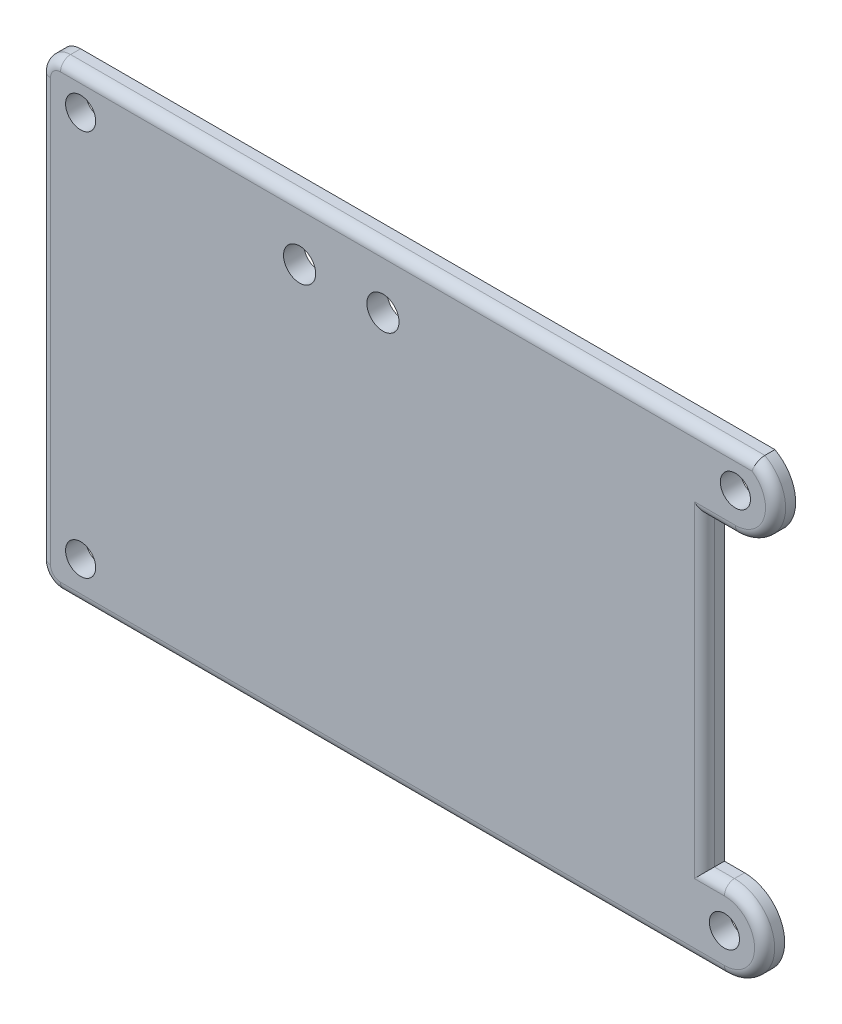
SolidWorks part; units mm, degrees
note: The reader was unsure of these and kept them because the rebuilt part matched: shared geometry of "草图2<6>".
ref_plane "前视基准面" through (0, 0, 0) normal (0, 0, 1) x (1, 0, 0)
ref_plane "上视基准面" through (0, 0, 0) normal (0, 1, 0) x (1, 0, 0)
ref_plane "右视基准面" through (0, 0, 0) normal (1, 0, 0) x (0, 0, -1)
sketch "Model" plane through (0, 0, 0) normal (0, 0, 1) x (1, 0, 0)
  line L0 (0, 2.26) -> (0, 39.4058)
  line L1 (2.4326, 41.5) -> (50.1564, 41.5)
  line L2 (52.5, 39.422) -> (52.5, 2.28)
  line L3 (50.22, 0) -> (2.26, 0)
  line L4 (0.57, 8.85) -> (-6.93, 8.85)
  line L5 (-6.93, 8.85) -> (-6.93, 24.85)
  line L6 (-6.93, 24.85) -> (0.57, 24.85)
  line L7 (16.57, 8.85) -> (17.57, 8.85)
  line L8 (17.57, 8.85) -> (17.57, 10.85)
  line L9 (17.57, 22.85) -> (17.57, 24.85)
  line L10 (17.57, 24.85) -> (16.57, 24.85)
  line L11 (24.196, 8.775) -> (23.307, 8.775)
  line L12 (22.926, 9.156) -> (22.926, 9.664)
  line L13 (23.307, 10.045) -> (24.196, 10.045)
  line L14 (24.704, 10.045) -> (25.593, 10.045)
  line L15 (25.974, 9.664) -> (25.974, 9.156)
  line L16 (25.593, 8.775) -> (24.704, 8.775)
  line L17 (34.756, 17.315) -> (33.867, 17.315)
  line L18 (33.486, 17.696) -> (33.486, 18.204)
  line L19 (33.867, 18.585) -> (34.756, 18.585)
  line L20 (35.264, 18.585) -> (36.153, 18.585)
  line L21 (36.534, 18.204) -> (36.534, 17.696)
  line L22 (36.153, 17.315) -> (35.264, 17.315)
  line L23 (16.835, 4.806) -> (16.835, 3.917)
  line L24 (16.454, 3.536) -> (15.946, 3.536)
  line L25 (15.565, 3.917) -> (15.565, 4.806)
  line L26 (15.565, 5.314) -> (15.565, 6.203)
  line L27 (15.946, 6.584) -> (16.454, 6.584)
  line L28 (16.835, 6.203) -> (16.835, 5.314)
  line L29 (26.454, 3.425) -> (27.343, 3.425)
  line L30 (27.724, 3.044) -> (27.724, 2.536)
  line L31 (27.343, 2.155) -> (26.454, 2.155)
  line L32 (25.946, 2.155) -> (25.057, 2.155)
  line L33 (24.676, 2.536) -> (24.676, 3.044)
  line L34 (25.057, 3.425) -> (25.946, 3.425)
  line L35 (18.255, 4.756) -> (18.255, 3.867)
  line L36 (17.874, 3.486) -> (17.366, 3.486)
  line L37 (16.985, 3.867) -> (16.985, 4.756)
  line L38 (16.985, 5.264) -> (16.985, 6.153)
  line L39 (17.366, 6.534) -> (17.874, 6.534)
  line L40 (18.255, 6.153) -> (18.255, 5.264)
  line L41 (12.8, 35.75) -> (12.8, 38.8)
  line L42 (12.8, 38.8) -> (14.05, 39.95)
  line L43 (14.05, 39.95) -> (16.45, 39.95)
  line L44 (16.45, 39.95) -> (17.6, 38.9)
  line L45 (17.6, 38.9) -> (17.6, 35.7)
  line L46 (17.6, 35.7) -> (16.45, 34.65)
  line L47 (16.45, 34.65) -> (14, 34.65)
  line L48 (14, 34.65) -> (12.8, 35.75)
  line L49 (3.87, 5.53) -> (6.67, 5.53)
  line L50 (6.67, 5.53) -> (6.67, 4.13)
  line L51 (6.67, 4.13) -> (3.87, 4.13)
  line L52 (3.87, 4.13) -> (3.87, 5.53)
  line L53 (20.8, 6.56) -> (20.8, 9.36)
  line L54 (20.8, 9.36) -> (22.2, 9.36)
  line L55 (22.2, 9.36) -> (22.2, 6.56)
  line L56 (22.2, 6.56) -> (20.8, 6.56)
  line L57 (8.21, 6.97) -> (8.21, 4.17)
  line L58 (8.21, 4.17) -> (6.81, 4.17)
  line L59 (6.81, 4.17) -> (6.81, 6.97)
  line L60 (6.81, 6.97) -> (8.21, 6.97)
  line L61 (10.82, 29.94) -> (10.82, 27.14)
  line L62 (10.82, 27.14) -> (9.42, 27.14)
  line L63 (9.42, 27.14) -> (9.42, 29.94)
  line L64 (9.42, 29.94) -> (10.82, 29.94)
  line L65 (33.69, 12.87) -> (30.89, 12.87)
  line L66 (30.89, 12.87) -> (30.89, 14.27)
  line L67 (30.89, 14.27) -> (33.69, 14.27)
  line L68 (33.69, 14.27) -> (33.69, 12.87)
  line L69 (14.93, 29.94) -> (14.93, 27.14)
  line L70 (14.93, 27.14) -> (13.53, 27.14)
  line L71 (13.53, 27.14) -> (13.53, 29.94)
  line L72 (13.53, 29.94) -> (14.93, 29.94)
  line L73 (26.13, 4.53) -> (26.37, 4.53)
  line L74 (26.37, 4.53) -> (26.37, 7.36)
  line L75 (26.37, 7.36) -> (26.13, 7.36)
  line L76 (22.89, 4.53) -> (22.6, 4.53)
  line L77 (22.6, 4.53) -> (22.6, 7.37)
  line L78 (22.6, 7.37) -> (22.87, 7.37)
  line L79 (1.79, 29.79) -> (6.87, 29.79)
  line L80 (6.87, 29.79) -> (6.87, 27.25)
  line L81 (6.87, 27.25) -> (1.79, 27.25)
  line L82 (1.79, 27.25) -> (1.79, 29.79)
  line L83 (29.996, 38.955) -> (29.107, 38.955)
  line L84 (28.726, 39.336) -> (28.726, 39.844)
  line L85 (29.107, 40.225) -> (29.996, 40.225)
  line L86 (30.504, 40.225) -> (31.393, 40.225)
  line L87 (31.774, 39.844) -> (31.774, 39.336)
  line L88 (31.393, 38.955) -> (30.504, 38.955)
  line L89 (35.825, 11.706) -> (35.825, 10.817)
  line L90 (35.444, 10.436) -> (34.936, 10.436)
  line L91 (34.555, 10.817) -> (34.555, 11.706)
  line L92 (34.555, 12.214) -> (34.555, 13.103)
  line L93 (34.936, 13.484) -> (35.444, 13.484)
  line L94 (35.825, 13.103) -> (35.825, 12.214)
  line L95 (31.416, 6.905) -> (30.527, 6.905)
  line L96 (30.146, 7.286) -> (30.146, 7.794)
  line L97 (30.527, 8.175) -> (31.416, 8.175)
  line L98 (31.924, 8.175) -> (32.813, 8.175)
  line L99 (33.194, 7.794) -> (33.194, 7.286)
  line L100 (32.813, 6.905) -> (31.924, 6.905)
  line L101 (27.125, 13.384) -> (27.125, 14.273)
  line L102 (27.506, 14.654) -> (28.014, 14.654)
  line L103 (28.395, 14.273) -> (28.395, 13.384)
  line L104 (28.395, 12.876) -> (28.395, 11.987)
  line L105 (28.014, 11.606) -> (27.506, 11.606)
  line L106 (27.125, 11.987) -> (27.125, 12.876)
  line L107 (2.726, 5.765) -> (1.837, 5.765)
  line L108 (1.456, 6.146) -> (1.456, 6.654)
  line L109 (1.837, 7.035) -> (2.726, 7.035)
  line L110 (3.234, 7.035) -> (4.123, 7.035)
  line L111 (4.504, 6.654) -> (4.504, 6.146)
  line L112 (4.123, 5.765) -> (3.234, 5.765)
  line L113 (38.274, 36.345) -> (39.163, 36.345)
  line L114 (39.544, 35.964) -> (39.544, 35.456)
  line L115 (39.163, 35.075) -> (38.274, 35.075)
  line L116 (37.766, 35.075) -> (36.877, 35.075)
  line L117 (36.496, 35.456) -> (36.496, 35.964)
  line L118 (36.877, 36.345) -> (37.766, 36.345)
  line L119 (35.295, 38.504) -> (35.295, 39.393)
  line L120 (35.676, 39.774) -> (36.184, 39.774)
  line L121 (36.565, 39.393) -> (36.565, 38.504)
  line L122 (36.565, 37.996) -> (36.565, 37.107)
  line L123 (36.184, 36.726) -> (35.676, 36.726)
  line L124 (35.295, 37.107) -> (35.295, 37.996)
  line L125 (31.265, 4.376) -> (31.265, 3.487)
  line L126 (30.884, 3.106) -> (30.376, 3.106)
  line L127 (29.995, 3.487) -> (29.995, 4.376)
  line L128 (29.995, 4.884) -> (29.995, 5.773)
  line L129 (30.376, 6.154) -> (30.884, 6.154)
  line L130 (31.265, 5.773) -> (31.265, 4.884)
  line L131 (33.42, 4.7325) -> (33.42, 6.15)
  line L132 (33.42, 6.15) -> (31.5, 6.15)
  line L133 (31.5, 6.15) -> (31.5, 4.7325)
  line L134 (33.42, 2.8275) -> (33.42, 1.43)
  line L135 (33.42, 1.43) -> (31.5, 1.43)
  line L136 (31.5, 1.43) -> (31.5, 2.8275)
  line L137 (37.99, 12.2925) -> (37.99, 13.71)
  line L138 (37.99, 13.71) -> (36.07, 13.71)
  line L139 (36.07, 13.71) -> (36.07, 12.2925)
  line L140 (37.99, 10.3875) -> (37.99, 8.99)
  line L141 (37.99, 8.99) -> (36.07, 8.99)
  line L142 (36.07, 8.99) -> (36.07, 10.3875)
  line L143 (37.074, 38.3336) -> (37.074, 37.343)
  line L144 (37.582, 36.835) -> (38.6488, 36.835)
  line L145 (39.106, 37.3176) -> (39.106, 38.3336)
  line L146 (37.074, 39.1464) -> (37.074, 40.137)
  line L147 (37.582, 40.645) -> (38.6488, 40.645)
  line L148 (39.106, 40.1624) -> (39.106, 39.1464)
  line L149 (33.975, 16.983) -> (31.689, 16.983)
  line L150 (31.689, 16.983) -> (31.689, 14.697)
  line L151 (31.689, 14.697) -> (33.975, 14.697)
  line L152 (35.245, 16.983) -> (37.15, 16.983)
  line L153 (37.15, 16.983) -> (37.531, 16.602)
  line L154 (37.531, 16.602) -> (37.531, 15.078)
  line L155 (37.531, 15.078) -> (37.15, 14.697)
  line L156 (37.15, 14.697) -> (35.245, 14.697)
  line L157 (21.1, 35.75) -> (21.1, 38.8)
  line L158 (21.1, 38.8) -> (22.35, 39.95)
  line L159 (22.35, 39.95) -> (24.75, 39.95)
  line L160 (24.75, 39.95) -> (25.9, 38.9)
  line L161 (25.9, 38.9) -> (25.9, 35.7)
  line L162 (25.9, 35.7) -> (24.75, 34.65)
  line L163 (24.75, 34.65) -> (22.3, 34.65)
  line L164 (22.3, 34.65) -> (21.1, 35.75)
  line L165 (5.44, 35.75) -> (5.44, 38.8)
  line L166 (5.44, 38.8) -> (6.69, 39.95)
  line L167 (6.69, 39.95) -> (9.09, 39.95)
  line L168 (9.09, 39.95) -> (10.24, 38.9)
  line L169 (10.24, 38.9) -> (10.24, 35.7)
  line L170 (10.24, 35.7) -> (9.09, 34.65)
  line L171 (9.09, 34.65) -> (6.64, 34.65)
  line L172 (6.64, 34.65) -> (5.44, 35.75)
  line L173 (34.57, 3.22) -> (38.57, 3.22)
  line L174 (38.57, 3.22) -> (38.57, 8.72)
  line L175 (38.57, 8.72) -> (34.57, 8.72)
  line L176 (34.57, 8.72) -> (34.57, 3.22)
  line L177 (39.81, 30.07) -> (37.01, 30.07)
  line L178 (37.01, 30.07) -> (37.01, 31.47)
  line L179 (37.01, 31.47) -> (39.81, 31.47)
  line L180 (39.81, 31.47) -> (39.81, 30.07)
  line L181 (28.51, 40.17) -> (28.51, 37.37)
  line L182 (28.51, 37.37) -> (27.11, 37.37)
  line L183 (27.11, 37.37) -> (27.11, 40.17)
  line L184 (27.11, 40.17) -> (28.51, 40.17)
  line L185 (32.06, 40.25) -> (34.86, 40.25)
  line L186 (34.86, 40.25) -> (34.86, 38.85)
  line L187 (34.86, 38.85) -> (32.06, 38.85)
  line L188 (32.06, 38.85) -> (32.06, 40.25)
  line L189 (28.56, 11.71) -> (28.56, 14.51)
  line L190 (28.56, 14.51) -> (29.96, 14.51)
  line L191 (29.96, 14.51) -> (29.96, 11.71)
  line L192 (29.96, 11.71) -> (28.56, 11.71)
  line L193 (25.54, 13.29) -> (25.54, 16.09)
  line L194 (25.54, 16.09) -> (26.94, 16.09)
  line L195 (26.94, 16.09) -> (26.94, 13.29)
  line L196 (26.94, 13.29) -> (25.54, 13.29)
  line L197 (27.11, 11.4) -> (29.91, 11.4)
  line L198 (29.91, 11.4) -> (29.91, 10)
  line L199 (29.91, 10) -> (27.11, 10)
  line L200 (27.11, 10) -> (27.11, 11.4)
  line L201 (29.06, 8.4) -> (26.26, 8.4)
  line L202 (26.26, 8.4) -> (26.26, 9.8)
  line L203 (26.26, 9.8) -> (29.06, 9.8)
  line L204 (29.06, 9.8) -> (29.06, 8.4)
  line L205 (18.53, 32.56) -> (18.53, 29.76)
  line L206 (18.53, 29.76) -> (17.13, 29.76)
  line L207 (17.13, 29.76) -> (17.13, 32.56)
  line L208 (17.13, 32.56) -> (18.53, 32.56)
  line L209 (5.02, 31.95) -> (2.22, 31.95)
  line L210 (2.22, 31.95) -> (2.22, 33.35)
  line L211 (2.22, 33.35) -> (5.02, 33.35)
  line L212 (5.02, 33.35) -> (5.02, 31.95)
  line L213 (9.22, 29.96) -> (9.22, 27.16)
  line L214 (9.22, 27.16) -> (7.82, 27.16)
  line L215 (7.82, 27.16) -> (7.82, 29.96)
  line L216 (7.82, 29.96) -> (9.22, 29.96)
  line L217 (25.54, 18.87) -> (28.34, 18.87)
  line L218 (28.34, 18.87) -> (28.34, 17.47)
  line L219 (28.34, 17.47) -> (25.54, 17.47)
  line L220 (25.54, 17.47) -> (25.54, 18.87)
  line L221 (28.31, 19.13) -> (25.51, 19.13)
  line L222 (25.51, 19.13) -> (25.51, 20.53)
  line L223 (25.51, 20.53) -> (28.31, 20.53)
  line L224 (28.31, 20.53) -> (28.31, 19.13)
  line L225 (8.87, 4.41) -> (8.87, 7.21)
  line L226 (8.87, 7.21) -> (10.27, 7.21)
  line L227 (10.27, 7.21) -> (10.27, 4.41)
  line L228 (10.27, 4.41) -> (8.87, 4.41)
  line L229 (11.05, 4.16) -> (11.05, 6.96)
  line L230 (11.05, 6.96) -> (12.45, 6.96)
  line L231 (12.45, 6.96) -> (12.45, 4.16)
  line L232 (12.45, 4.16) -> (11.05, 4.16)
  line L233 (7.61, 30.34) -> (4.81, 30.34)
  line L234 (4.81, 30.34) -> (4.81, 31.74)
  line L235 (4.81, 31.74) -> (7.61, 31.74)
  line L236 (7.61, 31.74) -> (7.61, 30.34)
  line L237 (4.24, 30.32) -> (1.44, 30.32)
  line L238 (1.44, 30.32) -> (1.44, 31.72)
  line L239 (1.44, 31.72) -> (4.24, 31.72)
  line L240 (4.24, 31.72) -> (4.24, 30.32)
  line L241 (39.81, 31.61) -> (37.01, 31.61)
  line L242 (37.01, 31.61) -> (37.01, 33.01)
  line L243 (37.01, 33.01) -> (39.81, 33.01)
  line L244 (39.81, 33.01) -> (39.81, 31.61)
  line L245 (30.83, 8.94) -> (30.83, 8.7)
  line L246 (30.83, 8.7) -> (33.66, 8.7)
  line L247 (33.66, 8.7) -> (33.66, 8.94)
  line L248 (30.83, 12.18) -> (30.83, 12.47)
  line L249 (30.83, 12.47) -> (33.67, 12.47)
  line L250 (33.67, 12.47) -> (33.67, 12.2)
  line L251 (51.33, 22.79) -> (51.33, 33.29)
  line L252 (51.33, 33.29) -> (45.93, 33.29)
  line L253 (45.93, 33.29) -> (45.93, 22.79)
  line L254 (45.93, 22.79) -> (46.63, 22.09)
  line L255 (46.63, 22.09) -> (50.63, 22.09)
  line L256 (50.63, 22.09) -> (51.33, 22.79)
  line L257 (48.63, 35.31) -> (48.63, 33.278)
  line L258 (49.646, 34.294) -> (47.614, 34.294)
  line L259 (51.38, 7.21) -> (51.38, 17.71)
  line L260 (51.38, 17.71) -> (45.98, 17.71)
  line L261 (45.98, 17.71) -> (45.98, 7.21)
  line L262 (45.98, 7.21) -> (46.68, 6.51)
  line L263 (46.68, 6.51) -> (50.68, 6.51)
  line L264 (50.68, 6.51) -> (51.38, 7.21)
  line L265 (48.68, 19.73) -> (48.68, 17.698)
  line L266 (49.696, 18.714) -> (47.664, 18.714)
  line L267 (31.402, 24.62) -> (31.402, 19.54)
  line L268 (31.402, 19.54) -> (34.958, 19.54)
  line L269 (34.958, 19.54) -> (34.958, 24.62)
  line L270 (34.958, 24.62) -> (31.402, 24.62)
  line L271 (33.942, 24.62) -> (33.942, 24.112)
  line L272 (33.942, 24.112) -> (32.418, 24.112)
  line L273 (32.418, 24.112) -> (32.418, 24.62)
  line L274 (35.323, 25.5545) -> (37.482, 25.5545)
  line L275 (37.482, 25.5545) -> (37.482, 29.7455)
  line L276 (37.482, 29.7455) -> (35.323, 29.7455)
  line L277 (30.497, 25.5545) -> (28.338, 25.5545)
  line L278 (28.338, 25.5545) -> (28.338, 29.7455)
  line L279 (28.338, 29.7455) -> (30.497, 29.7455)
  line L280 (39.675, 36.4523) -> (39.675, 38.9337)
  line L281 (39.675, 38.9337) -> (39.6757, 38.9337)
  line L282 (39.6757, 38.9337) -> (39.6757, 41.34)
  line L283 (39.6757, 41.34) -> (47.0987, 41.34)
  line L284 (47.0987, 41.34) -> (47.0987, 36.4523)
  line L285 (47.0987, 36.4523) -> (39.675, 36.4523)
  line L286 (39.674, 41.32) -> (47.0987, 41.32)
  line L287 (47.0987, 41.32) -> (47.0987, 41.84)
  line L288 (47.0987, 41.84) -> (39.674, 41.84)
  line L289 (39.674, 41.84) -> (39.674, 41.32)
  line L290 (40.55, 41.34) -> (40.12, 41.77)
  line L291 (46.28, 41.37) -> (46.71, 41.8)
  line L292 (35.28, 32.52) -> (35.28, 31.92)
  line L293 (35.28, 31.92) -> (34.88, 31.52)
  line L294 (34.88, 31.52) -> (34.38, 31.52)
  line L295 (34.98, 36.32) -> (34.98, 36.82)
  line L296 (34.98, 36.82) -> (34.48, 36.82)
  line L297 (29.98, 36.32) -> (29.98, 36.82)
  line L298 (29.98, 36.82) -> (30.48, 36.82)
  line L299 (29.98, 32.32) -> (29.98, 31.82)
  line L300 (29.98, 31.82) -> (30.48, 31.82)
  arc A0 (0, 2.26) -> (2.26, 0) centre (2.5947, 2.5947) ccw
  arc A1 (2.4326, 41.5) -> (0, 39.4058) centre (2.365, 39.1186) ccw
  arc A2 (52.5, 39.422) -> (50.1564, 41.5) centre (50.2928, 39.2933) ccw
  arc A3 (50.22, 0) -> (52.5, 2.28) centre (50.2397, 2.2603) ccw
  circle A4 centre (2.26, 0) radius 0.0635
  circle A5 centre (0, 2.26) radius 0.0635
  circle A6 centre (0, 39.4058) radius 0.0635
  circle A7 centre (2.4326, 41.5) radius 0.0635
  circle A8 centre (50.1564, 41.5) radius 0.0635
  circle A9 centre (52.5, 39.422) radius 0.0635
  circle A10 centre (52.5, 2.28) radius 0.0635
  circle A11 centre (2, 39.5) radius 1.1
  circle A12 centre (50.5, 39.5) radius 1.1
  circle A13 centre (50.5, 2) radius 1.1
  circle A14 centre (2, 2) radius 1.1
  circle A15 centre (0.57, 8.85) radius 0.0635
  circle A16 centre (-6.93, 8.85) radius 0.0635
  circle A17 centre (-6.93, 24.85) radius 0.0635
  circle A18 centre (0.57, 24.85) radius 0.0635
  circle A19 centre (16.57, 8.85) radius 0.0635
  circle A20 centre (17.57, 8.85) radius 0.0635
  circle A21 centre (17.57, 10.85) radius 0.0635
  circle A22 centre (17.57, 22.85) radius 0.0635
  circle A23 centre (17.57, 24.85) radius 0.0635
  circle A24 centre (16.57, 24.85) radius 0.0635
  circle A25 centre (1.57, 7.55) radius 0.3606
  arc A26 (22.926, 9.156) -> (23.307, 8.775) centre (23.307, 9.156) ccw
  arc A27 (23.307, 10.045) -> (22.926, 9.664) centre (23.307, 9.664) ccw
  circle A28 centre (24.196, 8.775) radius 0.025
  circle A29 centre (23.307, 8.775) radius 0.025
  arc A30 (25.974, 9.664) -> (25.593, 10.045) centre (25.593, 9.664) ccw
  arc A31 (25.593, 8.775) -> (25.974, 9.156) centre (25.593, 9.156) ccw
  circle A32 centre (24.704, 10.045) radius 0.025
  circle A33 centre (25.593, 10.045) radius 0.025
  arc A34 (33.486, 17.696) -> (33.867, 17.315) centre (33.867, 17.696) ccw
  arc A35 (33.867, 18.585) -> (33.486, 18.204) centre (33.867, 18.204) ccw
  circle A36 centre (34.756, 17.315) radius 0.025
  circle A37 centre (33.867, 17.315) radius 0.025
  arc A38 (36.534, 18.204) -> (36.153, 18.585) centre (36.153, 18.204) ccw
  arc A39 (36.153, 17.315) -> (36.534, 17.696) centre (36.153, 17.696) ccw
  circle A40 centre (35.264, 18.585) radius 0.025
  circle A41 centre (36.153, 18.585) radius 0.025
  arc A42 (16.454, 3.536) -> (16.835, 3.917) centre (16.454, 3.917) ccw
  arc A43 (15.565, 3.917) -> (15.946, 3.536) centre (15.946, 3.917) ccw
  circle A44 centre (16.835, 4.806) radius 0.025
  circle A45 centre (16.835, 3.917) radius 0.025
  arc A46 (15.946, 6.584) -> (15.565, 6.203) centre (15.946, 6.203) ccw
  arc A47 (16.835, 6.203) -> (16.454, 6.584) centre (16.454, 6.203) ccw
  circle A48 centre (15.565, 5.314) radius 0.025
  circle A49 centre (15.565, 6.203) radius 0.025
  arc A50 (27.724, 3.044) -> (27.343, 3.425) centre (27.343, 3.044) ccw
  arc A51 (27.343, 2.155) -> (27.724, 2.536) centre (27.343, 2.536) ccw
  circle A52 centre (26.454, 3.425) radius 0.025
  circle A53 centre (27.343, 3.425) radius 0.025
  arc A54 (24.676, 2.536) -> (25.057, 2.155) centre (25.057, 2.536) ccw
  arc A55 (25.057, 3.425) -> (24.676, 3.044) centre (25.057, 3.044) ccw
  circle A56 centre (25.946, 2.155) radius 0.025
  circle A57 centre (25.057, 2.155) radius 0.025
  arc A58 (17.874, 3.486) -> (18.255, 3.867) centre (17.874, 3.867) ccw
  arc A59 (16.985, 3.867) -> (17.366, 3.486) centre (17.366, 3.867) ccw
  circle A60 centre (18.255, 4.756) radius 0.025
  circle A61 centre (18.255, 3.867) radius 0.025
  arc A62 (17.366, 6.534) -> (16.985, 6.153) centre (17.366, 6.153) ccw
  arc A63 (18.255, 6.153) -> (17.874, 6.534) centre (17.874, 6.153) ccw
  circle A64 centre (16.985, 5.264) radius 0.025
  circle A65 centre (16.985, 6.153) radius 0.025
  circle A66 centre (12.8, 35.75) radius 0.0375
  circle A67 centre (12.8, 38.8) radius 0.0375
  circle A68 centre (14.05, 39.95) radius 0.0375
  circle A69 centre (16.45, 39.95) radius 0.0375
  circle A70 centre (17.6, 38.9) radius 0.0375
  circle A71 centre (17.6, 35.7) radius 0.0375
  circle A72 centre (16.45, 34.65) radius 0.0375
  circle A73 centre (14, 34.65) radius 0.0375
  circle A74 centre (15.2, 37.3) radius 1.5
  circle A75 centre (15.2, 37.3) radius 0.7566
  circle A76 centre (3.87, 5.53) radius 0.0375
  circle A77 centre (6.67, 5.53) radius 0.0375
  circle A78 centre (6.67, 4.13) radius 0.0375
  circle A79 centre (3.87, 4.13) radius 0.0375
  circle A80 centre (20.8, 6.56) radius 0.0375
  circle A81 centre (20.8, 9.36) radius 0.0375
  circle A82 centre (22.2, 9.36) radius 0.0375
  circle A83 centre (22.2, 6.56) radius 0.0375
  circle A84 centre (8.21, 6.97) radius 0.0375
  circle A85 centre (8.21, 4.17) radius 0.0375
  circle A86 centre (6.81, 4.17) radius 0.0375
  circle A87 centre (6.81, 6.97) radius 0.0375
  circle A88 centre (10.82, 29.94) radius 0.0375
  circle A89 centre (10.82, 27.14) radius 0.0375
  circle A90 centre (9.42, 27.14) radius 0.0375
  circle A91 centre (9.42, 29.94) radius 0.0375
  circle A92 centre (33.69, 12.87) radius 0.0375
  circle A93 centre (30.89, 12.87) radius 0.0375
  circle A94 centre (30.89, 14.27) radius 0.0375
  circle A95 centre (33.69, 14.27) radius 0.0375
  circle A96 centre (14.93, 29.94) radius 0.0375
  circle A97 centre (14.93, 27.14) radius 0.0375
  circle A98 centre (13.53, 27.14) radius 0.0375
  circle A99 centre (13.53, 29.94) radius 0.0375
  circle A100 centre (26.13, 4.53) radius 0.05
  circle A101 centre (26.37, 4.53) radius 0.05
  circle A102 centre (26.37, 7.36) radius 0.05
  circle A103 centre (26.13, 7.36) radius 0.05
  circle A104 centre (22.89, 4.53) radius 0.05
  circle A105 centre (22.6, 4.53) radius 0.05
  circle A106 centre (22.6, 7.37) radius 0.05
  circle A107 centre (22.87, 7.37) radius 0.05
  circle A108 centre (1.79, 29.79) radius 0.0635
  circle A109 centre (6.87, 29.79) radius 0.0635
  circle A110 centre (6.87, 27.25) radius 0.0635
  circle A111 centre (1.79, 27.25) radius 0.0635
  arc A112 (28.726, 39.336) -> (29.107, 38.955) centre (29.107, 39.336) ccw
  arc A113 (29.107, 40.225) -> (28.726, 39.844) centre (29.107, 39.844) ccw
  circle A114 centre (29.996, 38.955) radius 0.025
  circle A115 centre (29.107, 38.955) radius 0.025
  arc A116 (31.774, 39.844) -> (31.393, 40.225) centre (31.393, 39.844) ccw
  arc A117 (31.393, 38.955) -> (31.774, 39.336) centre (31.393, 39.336) ccw
  circle A118 centre (30.504, 40.225) radius 0.025
  circle A119 centre (31.393, 40.225) radius 0.025
  arc A120 (35.444, 10.436) -> (35.825, 10.817) centre (35.444, 10.817) ccw
  arc A121 (34.555, 10.817) -> (34.936, 10.436) centre (34.936, 10.817) ccw
  circle A122 centre (35.825, 11.706) radius 0.025
  circle A123 centre (35.825, 10.817) radius 0.025
  arc A124 (34.936, 13.484) -> (34.555, 13.103) centre (34.936, 13.103) ccw
  arc A125 (35.825, 13.103) -> (35.444, 13.484) centre (35.444, 13.103) ccw
  circle A126 centre (34.555, 12.214) radius 0.025
  circle A127 centre (34.555, 13.103) radius 0.025
  arc A128 (30.146, 7.286) -> (30.527, 6.905) centre (30.527, 7.286) ccw
  arc A129 (30.527, 8.175) -> (30.146, 7.794) centre (30.527, 7.794) ccw
  circle A130 centre (31.416, 6.905) radius 0.025
  circle A131 centre (30.527, 6.905) radius 0.025
  arc A132 (33.194, 7.794) -> (32.813, 8.175) centre (32.813, 7.794) ccw
  arc A133 (32.813, 6.905) -> (33.194, 7.286) centre (32.813, 7.286) ccw
  circle A134 centre (31.924, 8.175) radius 0.025
  circle A135 centre (32.813, 8.175) radius 0.025
  arc A136 (27.506, 14.654) -> (27.125, 14.273) centre (27.506, 14.273) ccw
  arc A137 (28.395, 14.273) -> (28.014, 14.654) centre (28.014, 14.273) ccw
  circle A138 centre (27.125, 13.384) radius 0.025
  circle A139 centre (27.125, 14.273) radius 0.025
  arc A140 (28.014, 11.606) -> (28.395, 11.987) centre (28.014, 11.987) ccw
  arc A141 (27.125, 11.987) -> (27.506, 11.606) centre (27.506, 11.987) ccw
  circle A142 centre (28.395, 12.876) radius 0.025
  circle A143 centre (28.395, 11.987) radius 0.025
  arc A144 (1.456, 6.146) -> (1.837, 5.765) centre (1.837, 6.146) ccw
  arc A145 (1.837, 7.035) -> (1.456, 6.654) centre (1.837, 6.654) ccw
  circle A146 centre (2.726, 5.765) radius 0.025
  circle A147 centre (1.837, 5.765) radius 0.025
  arc A148 (4.504, 6.654) -> (4.123, 7.035) centre (4.123, 6.654) ccw
  arc A149 (4.123, 5.765) -> (4.504, 6.146) centre (4.123, 6.146) ccw
  circle A150 centre (3.234, 7.035) radius 0.025
  circle A151 centre (4.123, 7.035) radius 0.025
  arc A152 (39.544, 35.964) -> (39.163, 36.345) centre (39.163, 35.964) ccw
  arc A153 (39.163, 35.075) -> (39.544, 35.456) centre (39.163, 35.456) ccw
  circle A154 centre (38.274, 36.345) radius 0.025
  circle A155 centre (39.163, 36.345) radius 0.025
  arc A156 (36.496, 35.456) -> (36.877, 35.075) centre (36.877, 35.456) ccw
  arc A157 (36.877, 36.345) -> (36.496, 35.964) centre (36.877, 35.964) ccw
  circle A158 centre (37.766, 35.075) radius 0.025
  circle A159 centre (36.877, 35.075) radius 0.025
  arc A160 (35.676, 39.774) -> (35.295, 39.393) centre (35.676, 39.393) ccw
  arc A161 (36.565, 39.393) -> (36.184, 39.774) centre (36.184, 39.393) ccw
  circle A162 centre (35.295, 38.504) radius 0.025
  circle A163 centre (35.295, 39.393) radius 0.025
  arc A164 (36.184, 36.726) -> (36.565, 37.107) centre (36.184, 37.107) ccw
  arc A165 (35.295, 37.107) -> (35.676, 36.726) centre (35.676, 37.107) ccw
  circle A166 centre (36.565, 37.996) radius 0.025
  circle A167 centre (36.565, 37.107) radius 0.025
  arc A168 (30.884, 3.106) -> (31.265, 3.487) centre (30.884, 3.487) ccw
  arc A169 (29.995, 3.487) -> (30.376, 3.106) centre (30.376, 3.487) ccw
  circle A170 centre (31.265, 4.376) radius 0.025
  circle A171 centre (31.265, 3.487) radius 0.025
  arc A172 (30.376, 6.154) -> (29.995, 5.773) centre (30.376, 5.773) ccw
  arc A173 (31.265, 5.773) -> (30.884, 6.154) centre (30.884, 5.773) ccw
  circle A174 centre (29.995, 4.884) radius 0.025
  circle A175 centre (29.995, 5.773) radius 0.025
  circle A176 centre (33.42, 4.7325) radius 0.0635
  circle A177 centre (33.42, 6.15) radius 0.0635
  circle A178 centre (31.5, 6.15) radius 0.0635
  circle A179 centre (31.5, 4.7325) radius 0.0635
  circle A180 centre (33.42, 2.8275) radius 0.0635
  circle A181 centre (33.42, 1.43) radius 0.0635
  circle A182 centre (31.5, 1.43) radius 0.0635
  circle A183 centre (31.5, 2.8275) radius 0.0635
  circle A184 centre (37.99, 12.2925) radius 0.0635
  circle A185 centre (37.99, 13.71) radius 0.0635
  circle A186 centre (36.07, 13.71) radius 0.0635
  circle A187 centre (36.07, 12.2925) radius 0.0635
  circle A188 centre (37.99, 10.3875) radius 0.0635
  circle A189 centre (37.99, 8.99) radius 0.0635
  circle A190 centre (36.07, 8.99) radius 0.0635
  circle A191 centre (36.07, 10.3875) radius 0.0635
  arc A192 (37.074, 37.343) -> (37.582, 36.835) centre (37.582, 37.343) ccw
  arc A193 (38.6488, 36.835) -> (39.106, 37.3176) centre (38.6361, 37.3049) ccw
  circle A194 centre (37.074, 38.3336) radius 0.0254
  circle A195 centre (37.074, 37.343) radius 0.0254
  arc A196 (37.582, 40.645) -> (37.074, 40.137) centre (37.582, 40.137) ccw
  arc A197 (39.106, 40.1624) -> (38.6488, 40.645) centre (38.6361, 40.1751) ccw
  circle A198 centre (37.074, 39.1464) radius 0.0254
  circle A199 centre (37.074, 40.137) radius 0.0254
  circle A200 centre (33.975, 16.983) radius 0.0635
  circle A201 centre (31.689, 16.983) radius 0.0635
  circle A202 centre (31.689, 14.697) radius 0.0635
  circle A203 centre (33.975, 14.697) radius 0.0635
  circle A204 centre (35.245, 16.983) radius 0.0635
  circle A205 centre (37.15, 16.983) radius 0.0635
  circle A206 centre (37.531, 16.602) radius 0.0635
  circle A207 centre (37.531, 15.078) radius 0.0635
  circle A208 centre (37.15, 14.697) radius 0.0635
  circle A209 centre (35.245, 14.697) radius 0.0635
  circle A210 centre (21.1, 35.75) radius 0.0375
  circle A211 centre (21.1, 38.8) radius 0.0375
  circle A212 centre (22.35, 39.95) radius 0.0375
  circle A213 centre (24.75, 39.95) radius 0.0375
  circle A214 centre (25.9, 38.9) radius 0.0375
  circle A215 centre (25.9, 35.7) radius 0.0375
  circle A216 centre (24.75, 34.65) radius 0.0375
  circle A217 centre (22.3, 34.65) radius 0.0375
  circle A218 centre (23.5, 37.3) radius 1.5
  circle A219 centre (23.5, 37.3) radius 0.7566
  circle A220 centre (5.44, 35.75) radius 0.0375
  circle A221 centre (5.44, 38.8) radius 0.0375
  circle A222 centre (6.69, 39.95) radius 0.0375
  circle A223 centre (9.09, 39.95) radius 0.0375
  circle A224 centre (10.24, 38.9) radius 0.0375
  circle A225 centre (10.24, 35.7) radius 0.0375
  circle A226 centre (9.09, 34.65) radius 0.0375
  circle A227 centre (6.64, 34.65) radius 0.0375
  circle A228 centre (7.84, 37.3) radius 1.5
  circle A229 centre (7.84, 37.3) radius 0.7566
  circle A230 centre (34.57, 3.22) radius 0.0381
  circle A231 centre (38.57, 3.22) radius 0.0381
  circle A232 centre (38.57, 8.72) radius 0.0381
  circle A233 centre (34.57, 8.72) radius 0.0381
  circle A234 centre (39.81, 30.07) radius 0.0375
  circle A235 centre (37.01, 30.07) radius 0.0375
  circle A236 centre (37.01, 31.47) radius 0.0375
  circle A237 centre (39.81, 31.47) radius 0.0375
  circle A238 centre (28.51, 40.17) radius 0.0375
  circle A239 centre (28.51, 37.37) radius 0.0375
  circle A240 centre (27.11, 37.37) radius 0.0375
  circle A241 centre (27.11, 40.17) radius 0.0375
  circle A242 centre (32.06, 40.25) radius 0.0375
  circle A243 centre (34.86, 40.25) radius 0.0375
  circle A244 centre (34.86, 38.85) radius 0.0375
  circle A245 centre (32.06, 38.85) radius 0.0375
  circle A246 centre (28.56, 11.71) radius 0.0375
  circle A247 centre (28.56, 14.51) radius 0.0375
  circle A248 centre (29.96, 14.51) radius 0.0375
  circle A249 centre (29.96, 11.71) radius 0.0375
  circle A250 centre (25.54, 13.29) radius 0.0375
  circle A251 centre (25.54, 16.09) radius 0.0375
  circle A252 centre (26.94, 16.09) radius 0.0375
  circle A253 centre (26.94, 13.29) radius 0.0375
  circle A254 centre (27.11, 11.4) radius 0.0375
  circle A255 centre (29.91, 11.4) radius 0.0375
  circle A256 centre (29.91, 10) radius 0.0375
  circle A257 centre (27.11, 10) radius 0.0375
  circle A258 centre (29.06, 8.4) radius 0.0375
  circle A259 centre (26.26, 8.4) radius 0.0375
  circle A260 centre (26.26, 9.8) radius 0.0375
  circle A261 centre (29.06, 9.8) radius 0.0375
  circle A262 centre (18.53, 32.56) radius 0.0375
  circle A263 centre (18.53, 29.76) radius 0.0375
  circle A264 centre (17.13, 29.76) radius 0.0375
  circle A265 centre (17.13, 32.56) radius 0.0375
  circle A266 centre (5.02, 31.95) radius 0.0375
  circle A267 centre (2.22, 31.95) radius 0.0375
  circle A268 centre (2.22, 33.35) radius 0.0375
  circle A269 centre (5.02, 33.35) radius 0.0375
  circle A270 centre (9.22, 29.96) radius 0.0375
  circle A271 centre (9.22, 27.16) radius 0.0375
  circle A272 centre (7.82, 27.16) radius 0.0375
  circle A273 centre (7.82, 29.96) radius 0.0375
  circle A274 centre (25.54, 18.87) radius 0.0375
  circle A275 centre (28.34, 18.87) radius 0.0375
  circle A276 centre (28.34, 17.47) radius 0.0375
  circle A277 centre (25.54, 17.47) radius 0.0375
  circle A278 centre (28.31, 19.13) radius 0.0375
  circle A279 centre (25.51, 19.13) radius 0.0375
  circle A280 centre (25.51, 20.53) radius 0.0375
  circle A281 centre (28.31, 20.53) radius 0.0375
  circle A282 centre (8.87, 4.41) radius 0.0375
  circle A283 centre (8.87, 7.21) radius 0.0375
  circle A284 centre (10.27, 7.21) radius 0.0375
  circle A285 centre (10.27, 4.41) radius 0.0375
  circle A286 centre (11.05, 4.16) radius 0.0375
  circle A287 centre (11.05, 6.96) radius 0.0375
  circle A288 centre (12.45, 6.96) radius 0.0375
  circle A289 centre (12.45, 4.16) radius 0.0375
  circle A290 centre (7.61, 30.34) radius 0.0375
  circle A291 centre (4.81, 30.34) radius 0.0375
  circle A292 centre (4.81, 31.74) radius 0.0375
  circle A293 centre (7.61, 31.74) radius 0.0375
  circle A294 centre (4.24, 30.32) radius 0.0375
  circle A295 centre (1.44, 30.32) radius 0.0375
  circle A296 centre (1.44, 31.72) radius 0.0375
  circle A297 centre (4.24, 31.72) radius 0.0375
  circle A298 centre (39.81, 31.61) radius 0.0375
  circle A299 centre (37.01, 31.61) radius 0.0375
  circle A300 centre (37.01, 33.01) radius 0.0375
  circle A301 centre (39.81, 33.01) radius 0.0375
  circle A302 centre (30.83, 8.94) radius 0.05
  circle A303 centre (30.83, 8.7) radius 0.05
  circle A304 centre (33.66, 8.7) radius 0.05
  circle A305 centre (33.66, 8.94) radius 0.05
  circle A306 centre (30.83, 12.18) radius 0.05
  circle A307 centre (30.83, 12.47) radius 0.05
  circle A308 centre (33.67, 12.47) radius 0.05
  circle A309 centre (33.67, 12.2) radius 0.05
  circle A310 centre (33.43, 8.97) radius 0.2343
  circle A311 centre (51.33, 22.79) radius 0.0635
  circle A312 centre (51.33, 33.29) radius 0.0635
  circle A313 centre (45.93, 33.29) radius 0.0635
  circle A314 centre (45.93, 22.79) radius 0.0635
  circle A315 centre (46.63, 22.09) radius 0.0635
  circle A316 centre (50.63, 22.09) radius 0.0635
  circle A317 centre (48.63, 35.31) radius 0.0635
  circle A318 centre (48.63, 33.278) radius 0.0635
  circle A319 centre (49.646, 34.294) radius 0.0635
  circle A320 centre (47.614, 34.294) radius 0.0635
  circle A321 centre (51.38, 7.21) radius 0.0635
  circle A322 centre (51.38, 17.71) radius 0.0635
  circle A323 centre (45.98, 17.71) radius 0.0635
  circle A324 centre (45.98, 7.21) radius 0.0635
  circle A325 centre (46.68, 6.51) radius 0.0635
  circle A326 centre (50.68, 6.51) radius 0.0635
  circle A327 centre (48.68, 19.73) radius 0.0635
  circle A328 centre (48.68, 17.698) radius 0.0635
  circle A329 centre (49.696, 18.714) radius 0.0635
  circle A330 centre (47.664, 18.714) radius 0.0635
  circle A331 centre (31.402, 24.62) radius 0.0635
  circle A332 centre (31.402, 19.54) radius 0.0635
  circle A333 centre (34.958, 19.54) radius 0.0635
  circle A334 centre (34.958, 24.62) radius 0.0635
  circle A335 centre (30.132, 24.874) radius 0.1778
  circle A336 centre (33.942, 24.62) radius 0.0635
  circle A337 centre (33.942, 24.112) radius 0.0635
  circle A338 centre (32.418, 24.112) radius 0.0635
  circle A339 centre (32.418, 24.62) radius 0.0635
  circle A340 centre (35.323, 25.5545) radius 0.0635
  circle A341 centre (37.482, 25.5545) radius 0.0635
  circle A342 centre (37.482, 29.7455) radius 0.0635
  circle A343 centre (35.323, 29.7455) radius 0.0635
  circle A344 centre (30.497, 25.5545) radius 0.0635
  circle A345 centre (28.338, 25.5545) radius 0.0635
  circle A346 centre (28.338, 29.7455) radius 0.0635
  circle A347 centre (30.497, 29.7455) radius 0.0635
  circle A348 centre (39.675, 36.4523) radius 0.0375
  circle A349 centre (39.675, 38.9337) radius 0.0375
  circle A350 centre (39.6757, 38.9337) radius 0.0375
  circle A351 centre (39.6757, 41.34) radius 0.0375
  circle A352 centre (47.0987, 41.34) radius 0.0375
  circle A353 centre (47.0987, 36.4523) radius 0.0375
  circle A354 centre (39.674, 41.32) radius 0.0375
  circle A355 centre (47.0987, 41.32) radius 0.0375
  circle A356 centre (47.0987, 41.84) radius 0.0375
  circle A357 centre (39.674, 41.84) radius 0.0375
  circle A358 centre (40.55, 41.34) radius 0.0375
  circle A359 centre (40.12, 41.77) radius 0.0375
  circle A360 centre (46.28, 41.37) radius 0.0375
  circle A361 centre (46.71, 41.8) radius 0.0375
  circle A362 centre (35.28, 32.52) radius 0.05
  circle A363 centre (35.28, 31.92) radius 0.05
  circle A364 centre (34.88, 31.52) radius 0.05
  circle A365 centre (34.38, 31.52) radius 0.05
  circle A366 centre (34.98, 36.32) radius 0.05
  circle A367 centre (34.98, 36.82) radius 0.05
  circle A368 centre (34.48, 36.82) radius 0.05
  circle A369 centre (29.98, 36.32) radius 0.05
  circle A370 centre (29.98, 36.82) radius 0.05
  circle A371 centre (30.48, 36.82) radius 0.05
  circle A372 centre (29.98, 32.32) radius 0.05
  circle A373 centre (29.98, 31.82) radius 0.05
  circle A374 centre (30.48, 31.82) radius 0.05
sketch "草图2" plane through (0, 0, 0) normal (0, 0, 1) x (1, 0, 0)
  line L2 (-6.6015, 41.501) -> (53.5, 41.501)
  line L10 (-6.6015, -1) -> (53.5, -1)
  line L11 (53.5, 41.501) -> (53.5, -1)
  line L14 (-9.6015, 41.501) -> (-9.6015, 0) construction
  line L15 (-9.6015, 0) -> (0, 0) construction
  line L16 (0, 0) -> (52.5, 0) construction
  line L17 (52.5, 41.501) -> (52.5, 0) construction
  line L18 (-8.6015, -3) -> (0, -3)
  line L19 (0, -3) -> (55.5, -3)
  line L20 (55.5, 43.001) -> (55.5, -3)
  line L23 (0, 42.501) -> (53.5, 42.501) construction
  line L24 (0, 42.501) -> (-10.6015, 42.501) construction
  line L25 (0, 43.001) -> (55.5, 43.001)
  line L26 (0, 43.001) -> (-8.6015, 43.001)
  line L27 (0, 41.501) -> (-9.6015, 41.501) construction
  line L28 (0, 41.501) -> (52.5, 41.501) construction
  line L29 (0, 43.001) -> (52.5, 43.001) construction
  line L30 (0, 43.001) -> (-9.6015, 43.001) construction
  line L31 (-10.6015, 42.501) -> (-10.6015, -1) construction
  line L32 (53.5, 42.501) -> (53.5, -1) construction
  line L33 (-12.6015, 44.501) -> (-12.6015, -3) construction
  line L34 (0, 44.501) -> (-12.6015, 44.501) construction
  line L35 (0, 44.501) -> (55.5, 44.501) construction
  line L36 (55.5, 44.501) -> (55.5, -3) construction
  line L37 (-8.6015, 43.001) -> (-20.5, 43.001)
  line L38 (-22.5, 41.001) -> (-22.5, -1)
  line L39 (-20.5, -3) -> (-8.6015, -3)
  line L40 (55.5, 43.001) -> (65.5, 43.001)
  line L41 (67.5, 41.001) -> (67.5, -1)
  line L42 (65.5, -3) -> (55.5, -3)
  line L43 (52.5, 39.422) -> (52.5, 2.28) construction
  line L44 (-17.5, 22) -> (62.5, 22) construction
  line L45 (-10.6015, -1) -> (0, -1) construction
  line L46 (-8.6015, 39.501) -> (-6.6015, 39.501) construction
  line L47 (-1008.2876, 1) -> (-22.5, 1)
  line L48 (57.5, 5) -> (55.5, 5)
  line L49 (58.5907, 35.501) -> (55.5, 35.501)
  line L50 (-10.6015, 41.001) -> (-10.6015, -1)
  line L51 (-8.6015, 39.501) -> (-8.6015, 1)
  line L52 (0, -1) -> (53.5, -1) construction
  line L53 (-8.6015, 43.001) -> (-8.6015, -3) construction
  line L54 (-10.6015, 43.001) -> (-10.6015, -3) construction
  line L55 (-12.6015, -3) -> (0, -3) construction
  line L56 (2, 39.5) -> (2, 41.501)
  line L57 (2, 39.501) -> (17, 39.501) construction
  line L58 (51.5, 39.501) -> (51.5, 1)
  line L59 (2, 2) -> (2, -1)
  line L60 (-8.6015, 32.2775) -> (-6.6015, 32.2775)
  line L61 (-8.6015, 11.7225) -> (-6.6015, 11.7225)
  line L62 (-6.6015, 32.2775) -> (-6.6015, 11.7225)
  line L63 (50.5, 39.5) -> (50.5, 41.501)
  line L64 (35.5, 39.501) -> (35.5, 41.501)
  line L65 (17, 39.501) -> (17, 41.501)
  line L66 (17, 1) -> (17, -1)
  line L67 (-6.6015, 1) -> (51.5, 1) construction
  line L68 (50.5, 2) -> (50.5, -1)
  line L69 (35.5, -1) -> (35.5, 1)
  line L70 (51.5, 39.501) -> (58.5907, 39.501) construction
  line L71 (2, 1) -> (17, 1)
  line L72 (35.5, 1) -> (50.9583, 1)
  line L73 (35.5, 39.501) -> (50.5, 39.501) construction
  line L74 (-6.6015, 39.501) -> (51.5, 39.501) construction
  line L75 (2, 39.501) -> (17, 39.501)
  line L76 (35.5, 39.501) -> (50.5, 39.501)
  circle A0 centre (2, 39.5) radius 1.1 construction
  circle A1 centre (50.5, 39.5) radius 1.1 construction
  circle A2 centre (50.5, 2) radius 1.1 construction
  circle A3 centre (2, 2) radius 1.1 construction
  circle A4 centre (23.5, 37.3) radius 2.8844 construction
  circle A5 centre (-17.5, 22) radius 3.25
  circle A6 centre (62.5, 22) radius 3.25
  arc A7 (65.5, -3) -> (67.5, -1) centre (65.5, -1) ccw
  arc A8 (67.5, 41.001) -> (65.5, 43.001) centre (65.5, 41.001) ccw
  arc A9 (-20.5, 43.001) -> (-22.5, 41.001) centre (-20.5, 41.001) ccw
  arc A10 (-22.5, -1) -> (-20.5, -3) centre (-20.5, -1) ccw
  circle A11 centre (2, 39.5) radius 1.6
  circle A12 centre (50.5, 39.5) radius 1.6
  circle A13 centre (2, 2) radius 1.6
  circle A14 centre (50.5, 2) radius 1.6
  arc A15 (-0.8728, 41.501) -> (4.8728, 41.501) centre (2, 39.5) ccw
  arc A16 (47.6272, 41.501) -> (53.5, 37.6954) centre (50.5, 39.5) ccw
  arc A19 (4.6458, -1) -> (-0.6458, -1) centre (2, 2) ccw
  arc A20 (53.5, 4.6458) -> (47.8542, -1) centre (50.5, 2) ccw
  circle A21 centre (-6.6015, 39.501) radius 2 construction
  arc A22 (-8.6015, 36.0369) -> (-3.1374, 41.501) centre (-6.6015, 39.501) ccw
  circle A23 centre (-6.6015, 1) radius 2 construction
  arc A24 (-3.1374, -1) -> (-8.6015, 4.4641) centre (-6.6015, 1) ccw
  circle A25 centre (58.5907, 39.501) radius 2 construction
  arc A26 (58.5907, 35.501) -> (60.5272, 43.001) centre (58.5907, 39.501) ccw
  circle A27 centre (57.5, 1) radius 2 construction
  arc A28 (57.5, -3) -> (57.5, 5) centre (57.5, 1) ccw
  circle A29 centre (-6.6015, 39.501) radius 1.5
  circle A30 centre (58.5907, 39.501) radius 1.5
  circle A31 centre (57.5, 1) radius 1.5
  circle A32 centre (-6.6015, 1) radius 1.5
  arc A33 (-8.6015, 43.001) -> (-10.6015, 41.001) centre (-8.6015, 41.001) ccw
  arc A34 (-8.6015, -3) -> (-10.6015, -1) centre (-8.6015, -1) cw
  circle A35 centre (23.5, 37.3) radius 1.6
  circle A36 centre (15.2, 37.3) radius 1.6
  dimension "D1" = 2.2
  dimension "D5" = 6.5
  dimension "D6" = 6.5
  dimension "D11" = 2
  dimension "D12" = 4
  dimension "D13" = 8
  dimension "D14" = 4
  dimension "D15" = 2
  dimension "D16" = 4
  dimension "D17" = 8
  dimension "D18" = 4
  dimension "D19" = 3.2
  dimension "D20" = 3.2
  dimension "D21" = 3.2
  dimension "D22" = 3.2
  dimension "D24" = 2
  dimension "D25" = 3.2
  dimension "D31" = 3.2
  dimension "D2" = 80
  dimension "D7" = 10
  dimension "D8" = 5
  dimension "D9" = 5
  dimension "D10" = 23
  dimension "D26" = 15
  dimension "D28" = 15
  dimension "D29" = 15
  dimension "D30" = 15
  dimension "D3" = 2
  dimension "D4" = 1.5
  dimension "D23" = 2
  dimension "D27" = 2
extrude "凸台-拉伸1" add sketch "草图2" along normal blind 2 contours A24 L10 A19 A20 L11 A16 L2 A15 A22 L51 | L2 A15 A11 | A11 | L2 A16 L11 A12 | A12 | L11 A20 L10 A14 | A14 | L10 A19 A13 | A13 | L10 A24 L51 A23 | L26 L50 L18 L19 L20 L25 A23 L51 A21 L2 L11 L10 | L51 A22 L2 A21 | L49 A26 L40 L20 A25 | L42 A28 L48 L20 A27 | L62 L60 L51 L61 | A15 L75 L65 L2 | L75 A15 L2 L56 A11 | L75 A11 L56 | A16 L2 L64 L76 | L2 A16 L76 A12 L63 | L63 A12 L76 | L76 A16 L58 A12 | A20 L11 A16 L58 | L58 A20 L72 A14 | A20 L72 L69 L10 | L72 A20 L10 L68 A14 | L72 A14 L68 | A19 L10 L66 L71
extrude "凸台-拉伸2" add sketch "草图2<6>" against normal blind 1 contours L62 L60 L51 L61 | A19 L10 L66 L71 | L10 A19 L71 A13 L59 | L59 A13 L71 | A20 L72 L69 L10 | L72 A20 L10 L68 A14 | L72 A14 L68 | A15 L75 L65 L2 | L75 A15 L2 L56 A11 | L75 A11 L56 | A16 L2 L64 L76 | L2 A16 L76 A12 L63 | L63 A12 L76
sketch "草图2<6>" plane through (0, 0, 0) normal (0, 0, 1) x (1, 0, 0) same geometry as "草图2"
fillet "圆角1" radius 1 10 edges at (57.0454, 35.501, 2) (25.9629, 43.001, 2) (-10.0157, 42.4152, 2) (56.5, 5, 2) (61.5, 1, 2) (24.4492, -3, 2) (-10.0157, -2.4142, 2) (55.5, 20.2505, 2) (62.4637, 38.501, 2) (-10.6015, 20.0005, 2)
